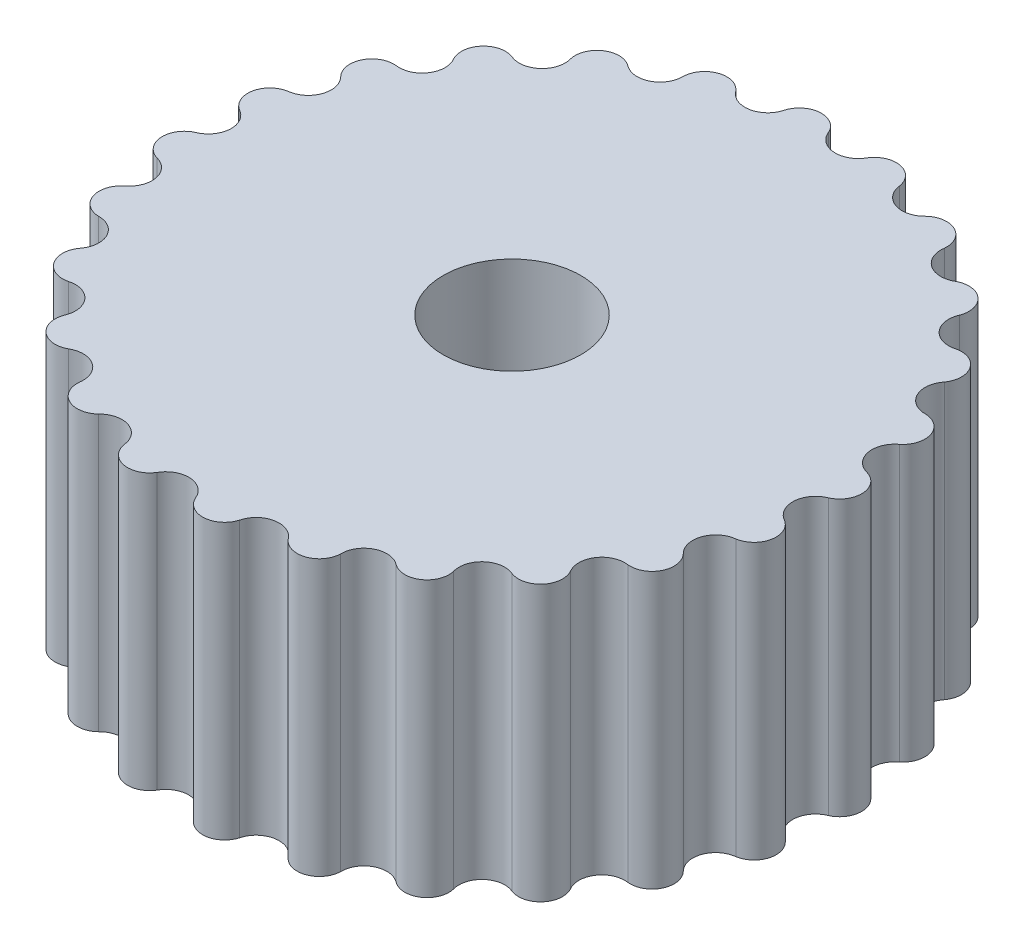
SolidWorks part; units mm, degrees
note: '?' marks a value the reader was unsure of.
ref_plane "Front Plane" through (0, 0, 0) normal (0, 0, 1) x (1, 0, 0)
ref_plane "Top Plane" through (0, 0, 0) normal (0, 1, 0) x (1, 0, 0)
ref_plane "Right Plane" through (0, 0, 0) normal (1, 0, 0) x (0, 0, -1)
sketch "Sketch1" plane through (0, 0, 0) normal (0, 1, 0) x (1, 0, 0)
  line L0 (0, 22) -> (0, 24) construction
  line L1 (2.8716, 21.8118) -> (3.1326, 23.7947) construction
  line L2 (5.694, 21.2504) -> (6.2117, 23.1822) construction
  line L3 (0, 23) -> (0, 5)
  line L4 (1.2941, 4.8296) -> (5.9528, 22.2163)
  circle A0 centre (0, 0) radius 22 construction
  arc A1 (0, 23) -> (3.0021, 22.8032) centre (1.5478, 23.6147) ccw
  arc A2 (6.2117, 23.1822) -> (0, 24) centre (0, 0) ccw construction
  arc A3 (3.0021, 22.8032) -> (5.9528, 22.2163) centre (4.3695, 21.9667) cw
  arc A4 (1.2941, 4.8296) -> (0, 5) centre (0, 0) ccw
  point P6 (0, 23)
  point P9 (3.0021, 22.8032)
  dimension "D1" = 44
  dimension "D2" = 2
  dimension "D3" = 10
extrude "Boss-Extrude1" add sketch "Sketch1" along normal blind 20
pattern_circular "CirPattern1" count 24 over 360 about axis through (0, 0, 0) along (0, 1, 0) of "Boss-Extrude1"
ref_axis "Axis1" through (0, 0, 0) along (0, 1, 0)?
sketch "Sketch2" plane through (0, 20, 0) normal (0, 1, 0) x (1, 0, 0)
  line L0 (0, 74.1691) -> (0, -78.0459) construction
  line L1 (19.05, 12.7) -> (26.67, 12.7)
  line L2 (19.05, 12.7) -> (19.05, -12.7)
  line L3 (19.05, -12.7) -> (26.67, -12.7)
  line L4 (26.67, 12.7) -> (26.67, -12.7)
  line L5 (-26.67, 12.7) -> (-26.67, -12.7)
  line L6 (-19.05, -12.7) -> (-26.67, -12.7)
  line L7 (-19.05, 12.7) -> (-19.05, -12.7)
  line L8 (-19.05, 12.7) -> (-26.67, 12.7)
  point P6 (19.05, 0)
  point P12 (-19.05, 0)
  dimension "D1" = 7.62
  dimension "D2" = 25.4
  dimension "D3" = 19.05
